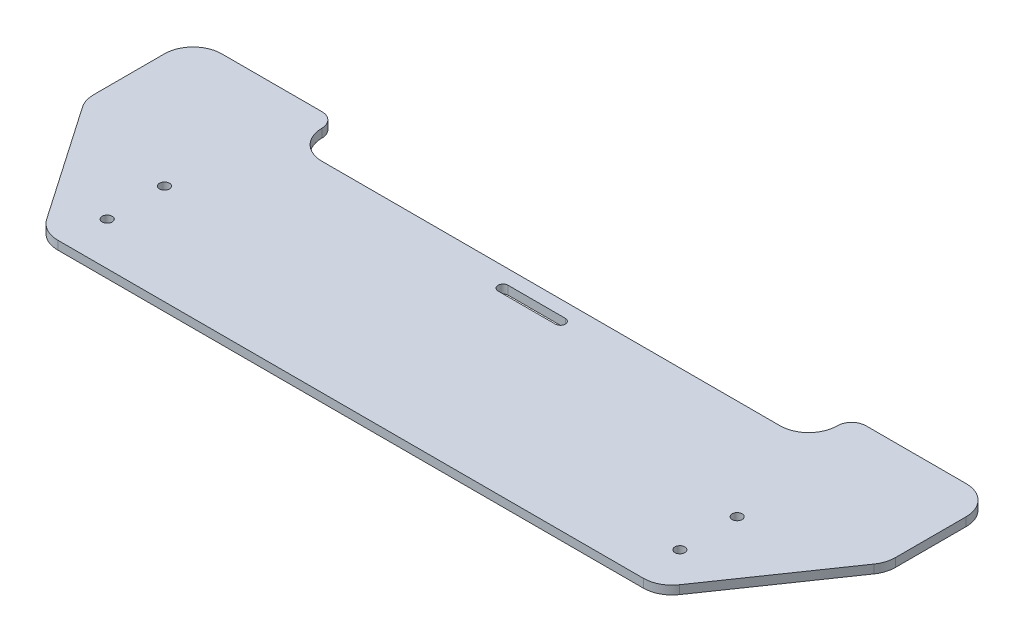
SolidWorks part; units mm, degrees
ref_plane "前视基准面" through (0, 0, 0) normal (0, 0, 1) x (1, 0, 0)
ref_plane "上视基准面" through (0, 0, 0) normal (0, 1, 0) x (1, 0, 0)
ref_plane "右视基准面" through (0, 0, 0) normal (1, 0, 0) x (0, 0, -1)
other "Configuration Table"
sketch "草图1" plane through (0, 0, 0) normal (0, 1, 0) x (1, 0, 0)
  line L0 (-138.2358, 19.5134) -> (-110.4921, -20.7712)
  line L2 (-140, 25.1854) -> (-140, 65)
  line L3 (-130.0992, 74.9008) -> (-100, 74.9008)
  line L5 (-200, -75) -> (0, 0) construction
  line L6 (-140, 74.9008) -> (0, 0) construction
  line L8 (-90, 64.9008) -> (-90, 54.9008)
  line L9 (-80, 44.9008) -> (80, 44.9008)
  line L12 (0, 0) -> (0, 50000) construction
  line L13 (-102.2563, -25.0992) -> (102.2563, -25.0992)
  line L15 (140, 74.9008) -> (0, 0) construction
  line L16 (200, -75) -> (0, 0) construction
  line L17 (90, 64.9008) -> (90, 54.9008)
  line L18 (130.0992, 74.9008) -> (100, 74.9008)
  line L19 (140, 25.1854) -> (140, 65)
  line L20 (138.2358, 19.5134) -> (110.4921, -20.7712)
  arc A2 (-90, 54.9008) -> (-80, 44.9008) centre (-80, 54.9008) ccw
  arc A3 (-90, 64.9008) -> (-100, 74.9008) centre (-100, 64.9008) ccw
  arc A5 (-140, 65) -> (-130.0992, 74.9008) centre (-130.0992, 65) cw
  arc A8 (-138.2358, 19.5134) -> (-140, 25.1854) centre (-130, 25.1854) cw
  arc A9 (-110.4921, -20.7712) -> (-102.2563, -25.0992) centre (-102.2563, -15.0992) ccw
  arc A10 (110.4921, -20.7712) -> (102.2563, -25.0992) centre (102.2563, -15.0992) cw
  arc A11 (138.2358, 19.5134) -> (140, 25.1854) centre (130, 25.1854) ccw
  arc A12 (140, 65) -> (130.0992, 74.9008) centre (130.0992, 65) ccw
  arc A13 (90, 64.9008) -> (100, 74.9008) centre (100, 64.9008) cw
  arc A14 (90, 54.9008) -> (80, 44.9008) centre (80, 54.9008) cw
  point P0 (0, 0)
  point P14 (0, 25)
  point P40 (0, 44.9008)
  point P41 (0, -25.0992)
  dimension "D4" = 50
  dimension "D1" = 280
  dimension "D2" = 100
  dimension "D3" = 30
extrude "凸台-拉伸1" add sketch "草图1" along normal blind 3
sketch "草图4" plane through (0, 3, 0) normal (0, 1, 0) x (1, 0, 0)
  line L0 (140, 25.1854) -> (140, 65) construction
  line L1 (140, 59.9008) -> (-147.1078, 59.9008)
  line L2 (140, 59.9008) -> (140, 79.3217)
  line L3 (140, 79.3217) -> (-147.1078, 79.3217)
  line L4 (-147.1078, 59.9008) -> (-147.1078, 79.3217)
  line L5 (-102.2563, -25.0992) -> (102.2563, -25.0992) construction
  dimension "D1" = 85
extrude "切除-拉伸2" cut sketch "草图4" against normal blind 18
fillet "圆角3" radius 5 2 edges at (-90, 1.5, -59.9008) (90, 1.5, -59.9008)
fillet "圆角4" radius 10 2 edges at (140, 1.5, -59.9008) (-140, 1.5, -59.9008)
sketch "草图5" plane through (0, 3, 0) normal (0, 1, 0) x (1, 0, 0)
  circle A0 centre (100, -10.0992) radius 1.75
  circle A1 centre (100, 9.9008) radius 1.75
  circle A2 centre (-100, -10.0992) radius 1.75
  circle A3 centre (-100, 9.9008) radius 1.75
extrude "切除-拉伸3" cut sketch "草图5" against normal blind 18
sketch "草图8" plane through (0, 3, 0) normal (0, 1, 0) x (1, 0, 0)
  line L0 (-10, 38.1508) -> (10, 38.1508) construction
  line L1 (-10, 39.9008) -> (10, 39.9008)
  line L2 (-10, 36.4008) -> (10, 36.4008)
  line L3 (80, 44.9008) -> (-80, 44.9008) construction
  arc A0 (-10, 39.9008) -> (-10, 36.4008) centre (-10, 38.1508) ccw
  arc A1 (10, 36.4008) -> (10, 39.9008) centre (10, 38.1508) ccw
  point P2 (0, 38.1508)
  dimension "D1" = 1.75
  dimension "D2" = 20
  dimension "D3" = 5
extrude "切除-拉伸6" cut sketch "草图8" against normal blind 3
